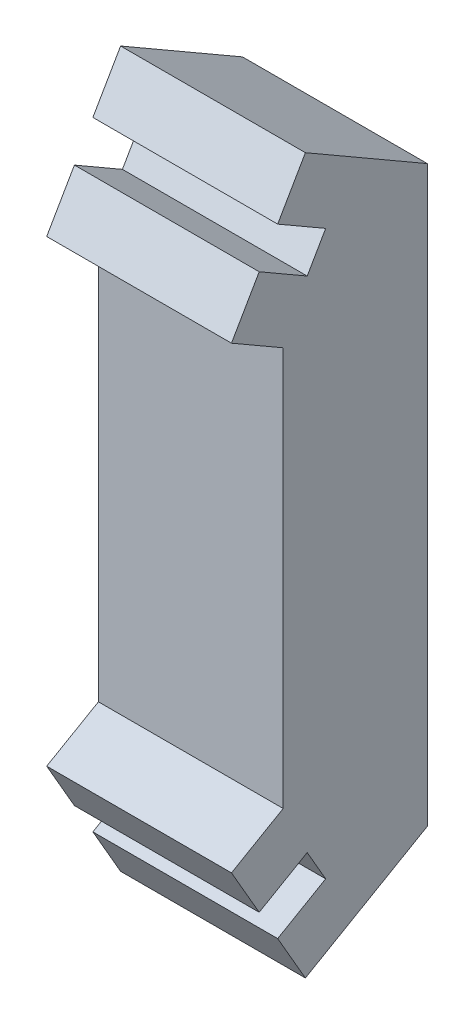
SolidWorks part; units mm, degrees
ref_plane "Спереди" through (0, 0, 0) normal (0, 0, 1) x (1, 0, 0)
ref_plane "Сверху" through (0, 0, 0) normal (0, 1, 0) x (1, 0, 0)
ref_plane "Справа" through (0, 0, 0) normal (1, 0, 0) x (0, 0, -1)
sketch "Эскиз1" plane through (0, 0, 0) normal (1, 0, 0) x (0, 0, -1)
  line L0 (-2.0398, 21.4769) -> (-2.0398, -5.5431) construction
  line L1 (-2.0398, 21.4769) -> (-4.6379, 22.9769)
  line L3 (-3.3389, 22.2269) -> (-2.3389, 23.9589) construction
  line L4 (-3.3389, -6.2931) -> (-2.3389, -8.0252) construction
  line L5 (-2.3389, 23.9589) -> (-1.0398, 23.2089)
  line L7 (-1.0398, 23.2089) -> (-1.0398, -7.2752) construction
  line L8 (-2.0398, 21.4769) -> (-1.0398, 23.2089)
  line L10 (-4.6379, 22.9769) -> (-6.1379, 20.3788)
  line L12 (-6.1379, 20.3788) -> (-3.3389, 18.7628)
  line L14 (-3.3389, -2.829) -> (-3.3389, 18.7628)
  line L15 (-2.3389, 23.9589) -> (-3.6379, 24.7089)
  line L17 (-3.6379, 24.7089) -> (-2.1379, 27.307)
  line L18 (-2.1379, 27.307) -> (4.4602, 23.4976)
  line L21 (4.4602, -7.5638) -> (4.4602, 23.4976)
  line L22 (-3.3389, 7.9669) -> (4.4602, 7.9669) construction
  line L23 (-2.1379, -11.3732) -> (4.4602, -7.5638)
  line L24 (-3.6379, -8.7752) -> (-2.1379, -11.3732)
  line L25 (-2.3389, -8.0252) -> (-3.6379, -8.7752)
  line L26 (-6.1379, -4.445) -> (-3.3389, -2.829)
  line L27 (-4.6379, -7.0431) -> (-6.1379, -4.445)
  line L28 (-2.0398, -5.5431) -> (-1.0398, -7.2752)
  line L29 (-2.3389, -8.0252) -> (-1.0398, -7.2752)
  line L30 (-2.0398, -5.5431) -> (-4.6379, -7.0431)
  point P7 (-1.0398, 7.9669)
  point P12 (-2.0398, 7.9669)
  dimension "D1" = 3
  dimension "D2" = 13.51
  dimension "D3" = 5.5
  dimension "D5" = 60
  dimension "D7" = 2
  dimension "D8" = 3
  dimension "D9" = 3
extrude "Бобышка-Вытянуть1" add sketch "Эскиз1" along normal blind 10
